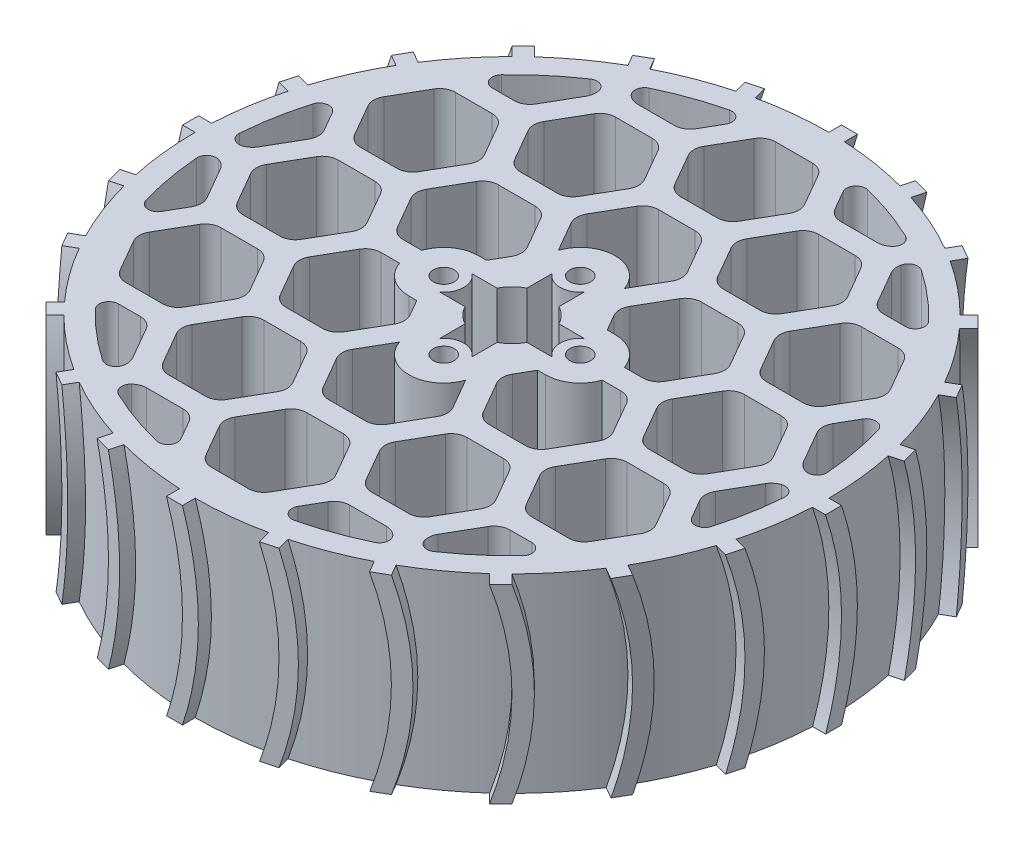
SolidWorks part; units mm, degrees
ref_plane "Front Plane" through (0, 0, 0) normal (0, 0, 1) x (1, 0, 0)
ref_plane "Top Plane" through (0, 0, 0) normal (0, 1, 0) x (1, 0, 0)
ref_plane "Right Plane" through (0, 0, 0) normal (1, 0, 0) x (0, 0, -1)
sketch "Sketch2" plane through (0, 0, 0) normal (0, 1, 0) x (1, 0, 0)
  line L0 (-17.7275, -5.0583) -> (-9.768, -5.0583)
  line L1 (-17.7275, 5.0583) -> (-9.768, 5.0583)
  line L2 (-21.548, 11) -> (-11, 11)
  line L3 (-21.548, -11) -> (-11, -11)
  line L4 (-21.548, 0) -> (0, 0) construction
  line L5 (11, 21.548) -> (11, 11)
  line L6 (-11, 21.548) -> (-11, 11)
  line L7 (5.0583, 17.7275) -> (5.0583, 9.768)
  line L8 (-5.0583, 17.7275) -> (-5.0583, 9.768)
  line L9 (21.548, -11) -> (11, -11)
  line L10 (21.548, 11) -> (11, 11)
  line L11 (17.7275, -5.0583) -> (9.768, -5.0583)
  line L12 (17.7275, 5.0583) -> (9.768, 5.0583)
  line L13 (-11, -21.548) -> (-11, -11)
  line L14 (11, -21.548) -> (11, -11)
  line L15 (-5.0583, -17.7275) -> (-5.0583, -9.768)
  line L16 (5.0583, -17.7275) -> (5.0583, -9.768)
  line L17 (0, 0) -> (-12.9904, 7.5) construction
  line L18 (-15.8771, -2.5) -> (-10.1036, -12.5)
  line L19 (-5.7735, -15) -> (5.7735, -15)
  line L20 (10.1036, -12.5) -> (15.8771, -2.5)
  line L21 (15.8771, 2.5) -> (10.1036, 12.5)
  line L22 (5.7735, 15) -> (-5.7735, 15)
  line L23 (-10.1036, 12.5) -> (-15.8771, 2.5)
  arc A0 (-21.548, 11) -> (-21.548, -11) centre (-21.548, 0) ccw
  arc A1 (-5.0583, 9.768) -> (-9.768, 5.0583) centre (0, 0) ccw
  circle A2 centre (-21.548, 0) radius 3.302
  circle A3 centre (-21.548, 0) radius 6.339
  arc A4 (-5.0583, 9.768) -> (-9.768, 5.0583) centre (0, 0) ccw
  arc A5 (11, 21.548) -> (-11, 21.548) centre (0, 21.548) ccw
  circle A6 centre (0, 21.548) radius 6.339
  circle A7 centre (0, 21.548) radius 3.302
  arc A8 (21.548, -11) -> (21.548, 11) centre (21.548, 0) ccw
  circle A9 centre (21.548, 0) radius 6.339
  circle A10 centre (21.548, 0) radius 3.302
  arc A11 (-11, -21.548) -> (11, -21.548) centre (0, -21.548) ccw
  circle A12 centre (0, -21.548) radius 6.339
  circle A13 centre (0, -21.548) radius 3.302
  arc A14 (9.768, 5.0583) -> (5.0583, 9.768) centre (0, 0) ccw
  arc A15 (5.0583, -9.768) -> (9.768, -5.0583) centre (0, 0) ccw
  arc A16 (-9.768, -5.0583) -> (-5.0583, -9.768) centre (0, 0) ccw
  circle A17 centre (0, 0) radius 100
  circle A18 centre (0, 0) radius 15 construction
  arc A19 (10.1036, 12.5) -> (5.7735, 15) centre (5.7735, 10) ccw
  arc A20 (15.8771, -2.5) -> (15.8771, 2.5) centre (11.547, 0) ccw
  arc A21 (10.1036, -12.5) -> (5.7735, -15) centre (5.7735, -10) cw
  arc A22 (-10.1036, -12.5) -> (-5.7735, -15) centre (-5.7735, -10) ccw
  arc A23 (-15.8771, -2.5) -> (-15.8771, 2.5) centre (-11.547, 0) cw
  arc A24 (-10.1036, 12.5) -> (-5.7735, 15) centre (-5.7735, 10) cw
  point P59 (0, 0)
  dimension "D1" = 6.604
  dimension "D2" = 12.678
  dimension "D3" = 11
  dimension "D8" = 22
  dimension "D10" = 200
  dimension "D12" = 5
  dimension "D4" = 21.548
  dimension "D5" = 7.9595
  dimension "D6" = 10.548
  dimension "D7" = 10.548
  dimension "D11" = 30
  dimension "D13" = 30
  dimension "D9" = 4
sketch "Sketch3" plane through (0, 0, 0) normal (0, 1, 0) x (1, 0, 0)
  line L0 (0, 0) -> (16.547, 0) construction
  line L1 (5.7735, 15) -> (-5.7735, 15)
  line L2 (-10.1036, 12.5) -> (-15.8771, 2.5)
  line L3 (-15.8771, -2.5) -> (-10.1036, -12.5)
  line L4 (-5.7735, -15) -> (5.7735, -15)
  line L5 (10.1036, -12.5) -> (15.8771, -2.5)
  line L6 (15.8771, 2.5) -> (10.1036, 12.5)
  line L7 (37.8164, 33.5) -> (26.2694, 33.5)
  line L8 (21.9393, 31) -> (16.1658, 21)
  line L9 (16.1658, 16) -> (21.9393, 6)
  line L10 (26.2694, 3.5) -> (37.8164, 3.5)
  line L11 (42.1466, 6) -> (47.9201, 16)
  line L12 (47.9201, 21) -> (42.1466, 31)
  line L13 (69.8594, 52) -> (58.3124, 52)
  line L14 (53.9823, 49.5) -> (48.2087, 39.5)
  line L15 (48.2087, 34.5) -> (53.9823, 24.5)
  line L16 (58.3124, 22) -> (69.8594, 22)
  line L17 (74.1895, 24.5) -> (79.963, 34.5)
  line L18 (79.963, 39.5) -> (74.1895, 49.5)
  line L19 (101.9023, 70.5) -> (90.3553, 70.5)
  line L20 (86.0252, 68) -> (80.2517, 58)
  line L21 (80.2517, 53) -> (86.0252, 43)
  line L22 (90.3553, 40.5) -> (101.9023, 40.5)
  line L23 (106.2324, 43) -> (112.006, 53)
  line L24 (112.006, 58) -> (106.2324, 68)
  line L25 (37.8164, 70.5) -> (26.2694, 70.5)
  line L26 (21.9393, 68) -> (16.1658, 58)
  line L27 (16.1658, 53) -> (21.9393, 43)
  line L28 (26.2694, 40.5) -> (37.8164, 40.5)
  line L29 (42.1466, 43) -> (47.9201, 53)
  line L30 (47.9201, 58) -> (42.1466, 68)
  line L31 (69.8594, 89) -> (58.3124, 89)
  line L32 (53.9823, 86.5) -> (48.2087, 76.5)
  line L33 (48.2087, 71.5) -> (53.9823, 61.5)
  line L34 (58.3124, 59) -> (69.8594, 59)
  line L35 (74.1895, 61.5) -> (79.963, 71.5)
  line L36 (79.963, 76.5) -> (74.1895, 86.5)
  line L37 (101.9023, 107.5) -> (90.3553, 107.5) [skipped]
  line L38 (86.0252, 105) -> (80.2517, 95) [skipped]
  line L39 (80.2517, 90) -> (86.0252, 80) [skipped]
  line L40 (90.3553, 77.5) -> (101.9023, 77.5) [skipped]
  line L41 (106.2324, 80) -> (112.006, 90) [skipped]
  line L42 (112.006, 95) -> (106.2324, 105) [skipped]
  line L43 (37.8164, 107.5) -> (26.2694, 107.5)
  line L44 (21.9393, 105) -> (16.1658, 95)
  line L45 (16.1658, 90) -> (21.9393, 80)
  line L46 (26.2694, 77.5) -> (37.8164, 77.5)
  line L47 (42.1466, 80) -> (47.9201, 90)
  line L48 (47.9201, 95) -> (42.1466, 105)
  line L49 (69.8594, 126) -> (58.3124, 126) [skipped]
  line L50 (53.9823, 123.5) -> (48.2087, 113.5) [skipped]
  line L51 (48.2087, 108.5) -> (53.9823, 98.5) [skipped]
  line L52 (58.3124, 96) -> (69.8594, 96) [skipped]
  line L53 (74.1895, 98.5) -> (79.963, 108.5) [skipped]
  line L54 (79.963, 113.5) -> (74.1895, 123.5) [skipped]
  line L55 (101.9023, 144.5) -> (90.3553, 144.5) [skipped]
  line L56 (86.0252, 142) -> (80.2517, 132) [skipped]
  line L57 (80.2517, 127) -> (86.0252, 117) [skipped]
  line L58 (90.3553, 114.5) -> (101.9023, 114.5) [skipped]
  line L59 (106.2324, 117) -> (112.006, 127) [skipped]
  line L60 (112.006, 132) -> (106.2324, 142) [skipped]
  line L61 (37.8164, 144.5) -> (26.2694, 144.5) [skipped]
  line L62 (21.9393, 142) -> (16.1658, 132) [skipped]
  line L63 (16.1658, 127) -> (21.9393, 117) [skipped]
  line L64 (26.2694, 114.5) -> (37.8164, 114.5) [skipped]
  line L65 (42.1466, 117) -> (47.9201, 127) [skipped]
  line L66 (47.9201, 132) -> (42.1466, 142) [skipped]
  line L67 (69.8594, 163) -> (58.3124, 163) [skipped]
  line L68 (53.9823, 160.5) -> (48.2087, 150.5) [skipped]
  line L69 (48.2087, 145.5) -> (53.9823, 135.5) [skipped]
  line L70 (58.3124, 133) -> (69.8594, 133) [skipped]
  line L71 (74.1895, 135.5) -> (79.963, 145.5) [skipped]
  line L72 (79.963, 150.5) -> (74.1895, 160.5) [skipped]
  line L73 (101.9023, 181.5) -> (90.3553, 181.5) [skipped]
  line L74 (86.0252, 179) -> (80.2517, 169) [skipped]
  line L75 (80.2517, 164) -> (86.0252, 154) [skipped]
  line L76 (90.3553, 151.5) -> (101.9023, 151.5) [skipped]
  line L77 (106.2324, 154) -> (112.006, 164) [skipped]
  line L78 (112.006, 169) -> (106.2324, 179) [skipped]
  line L79 (5.7735, 52) -> (-5.7735, 52) [skipped]
  line L80 (-10.1036, 49.5) -> (-15.8771, 39.5) [skipped]
  line L81 (-15.8771, 34.5) -> (-10.1036, 24.5) [skipped]
  line L82 (-5.7735, 22) -> (5.7735, 22) [skipped]
  line L83 (10.1036, 24.5) -> (15.8771, 34.5) [skipped]
  line L84 (15.8771, 39.5) -> (10.1036, 49.5) [skipped]
  line L85 (5.7735, 89) -> (-5.7735, 89) [skipped]
  line L86 (-10.1036, 86.5) -> (-15.8771, 76.5) [skipped]
  line L87 (-15.8771, 71.5) -> (-10.1036, 61.5) [skipped]
  line L88 (-5.7735, 59) -> (5.7735, 59) [skipped]
  line L89 (10.1036, 61.5) -> (15.8771, 71.5) [skipped]
  line L90 (15.8771, 76.5) -> (10.1036, 86.5) [skipped]
  line L91 (5.7735, 126) -> (-5.7735, 126) [skipped]
  line L92 (-10.1036, 123.5) -> (-15.8771, 113.5) [skipped]
  line L93 (-15.8771, 108.5) -> (-10.1036, 98.5) [skipped]
  line L94 (-5.7735, 96) -> (5.7735, 96) [skipped]
  line L95 (10.1036, 98.5) -> (15.8771, 108.5) [skipped]
  line L96 (15.8771, 113.5) -> (10.1036, 123.5) [skipped]
  line L97 (0, 0) -> (83.1384, 48) construction
  line L98 (112.006, 21) -> (106.2324, 31)
  line L99 (101.9023, 33.5) -> (90.3553, 33.5)
  line L100 (86.0252, 31) -> (80.2517, 21)
  line L101 (80.2517, 16) -> (86.0252, 6)
  line L102 (90.3553, 3.5) -> (101.9023, 3.5)
  line L103 (106.2324, 6) -> (112.006, 16)
  line L104 (112.006, -16) -> (106.2324, -6)
  line L105 (101.9023, -3.5) -> (90.3553, -3.5)
  line L106 (86.0252, -6) -> (80.2517, -16)
  line L107 (80.2517, -21) -> (86.0252, -31)
  line L108 (90.3553, -33.5) -> (101.9023, -33.5)
  line L109 (106.2324, -31) -> (112.006, -21)
  line L110 (112.006, -53) -> (106.2324, -43)
  line L111 (101.9023, -40.5) -> (90.3553, -40.5)
  line L112 (86.0252, -43) -> (80.2517, -53)
  line L113 (80.2517, -58) -> (86.0252, -68)
  line L114 (90.3553, -70.5) -> (101.9023, -70.5)
  line L115 (106.2324, -68) -> (112.006, -58)
  line L116 (79.963, -34.5) -> (74.1895, -24.5)
  line L117 (69.8594, -22) -> (58.3124, -22)
  line L118 (53.9823, -24.5) -> (48.2087, -34.5)
  line L119 (48.2087, -39.5) -> (53.9823, -49.5)
  line L120 (58.3124, -52) -> (69.8594, -52)
  line L121 (74.1895, -49.5) -> (79.963, -39.5)
  line L122 (79.963, 2.5) -> (74.1895, 12.5)
  line L123 (69.8594, 15) -> (58.3124, 15)
  line L124 (53.9823, 12.5) -> (48.2087, 2.5)
  line L125 (48.2087, -2.5) -> (53.9823, -12.5)
  line L126 (58.3124, -15) -> (69.8594, -15)
  line L127 (74.1895, -12.5) -> (79.963, -2.5)
  line L128 (47.9201, -16) -> (42.1466, -6)
  line L129 (37.8164, -3.5) -> (26.2694, -3.5)
  line L130 (21.9393, -6) -> (16.1658, -16)
  line L131 (16.1658, -21) -> (21.9393, -31)
  line L132 (26.2694, -33.5) -> (37.8164, -33.5)
  line L133 (42.1466, -31) -> (47.9201, -21)
  line L134 (74.1895, -86.5) -> (79.963, -76.5)
  line L135 (79.963, -71.5) -> (74.1895, -61.5)
  line L136 (69.8594, -59) -> (58.3124, -59)
  line L137 (53.9823, -61.5) -> (48.2087, -71.5)
  line L138 (48.2087, -76.5) -> (53.9823, -86.5)
  line L139 (58.3124, -89) -> (69.8594, -89)
  line L140 (42.1466, -105) -> (47.9201, -95)
  line L141 (47.9201, -90) -> (42.1466, -80)
  line L142 (37.8164, -77.5) -> (26.2694, -77.5)
  line L143 (21.9393, -80) -> (16.1658, -90)
  line L144 (16.1658, -95) -> (21.9393, -105)
  line L145 (26.2694, -107.5) -> (37.8164, -107.5)
  line L146 (10.1036, -123.5) -> (15.8771, -113.5)
  line L147 (15.8771, -108.5) -> (10.1036, -98.5)
  line L148 (5.7735, -96) -> (-5.7735, -96)
  line L149 (-10.1036, -98.5) -> (-15.8771, -108.5)
  line L150 (-15.8771, -113.5) -> (-10.1036, -123.5)
  line L151 (-5.7735, -126) -> (5.7735, -126)
  line L152 (10.1036, -86.5) -> (15.8771, -76.5)
  line L153 (15.8771, -71.5) -> (10.1036, -61.5)
  line L154 (5.7735, -59) -> (-5.7735, -59)
  line L155 (-10.1036, -61.5) -> (-15.8771, -71.5)
  line L156 (-15.8771, -76.5) -> (-10.1036, -86.5)
  line L157 (-5.7735, -89) -> (5.7735, -89)
  line L158 (42.1466, -68) -> (47.9201, -58)
  line L159 (47.9201, -53) -> (42.1466, -43)
  line L160 (37.8164, -40.5) -> (26.2694, -40.5)
  line L161 (21.9393, -43) -> (16.1658, -53)
  line L162 (16.1658, -58) -> (21.9393, -68)
  line L163 (26.2694, -70.5) -> (37.8164, -70.5)
  line L164 (10.1036, -49.5) -> (15.8771, -39.5)
  line L165 (15.8771, -34.5) -> (10.1036, -24.5)
  line L166 (5.7735, -22) -> (-5.7735, -22)
  line L167 (-10.1036, -24.5) -> (-15.8771, -34.5)
  line L168 (-15.8771, -39.5) -> (-10.1036, -49.5)
  line L169 (-5.7735, -52) -> (5.7735, -52)
  line L170 (-37.8164, -107.5) -> (-26.2694, -107.5)
  line L171 (-21.9393, -105) -> (-16.1658, -95)
  line L172 (-16.1658, -90) -> (-21.9393, -80)
  line L173 (-26.2694, -77.5) -> (-37.8164, -77.5)
  line L174 (-42.1466, -80) -> (-47.9201, -90)
  line L175 (-47.9201, -95) -> (-42.1466, -105)
  line L176 (-69.8594, -89) -> (-58.3124, -89)
  line L177 (-53.9823, -86.5) -> (-48.2087, -76.5)
  line L178 (-48.2087, -71.5) -> (-53.9823, -61.5)
  line L179 (-58.3124, -59) -> (-69.8594, -59)
  line L180 (-74.1895, -61.5) -> (-79.963, -71.5)
  line L181 (-79.963, -76.5) -> (-74.1895, -86.5)
  line L182 (-101.9023, -70.5) -> (-90.3553, -70.5)
  line L183 (-86.0252, -68) -> (-80.2517, -58)
  line L184 (-80.2517, -53) -> (-86.0252, -43)
  line L185 (-90.3553, -40.5) -> (-101.9023, -40.5)
  line L186 (-106.2324, -43) -> (-112.006, -53)
  line L187 (-112.006, -58) -> (-106.2324, -68)
  line L188 (-69.8594, -52) -> (-58.3124, -52)
  line L189 (-53.9823, -49.5) -> (-48.2087, -39.5)
  line L190 (-48.2087, -34.5) -> (-53.9823, -24.5)
  line L191 (-58.3124, -22) -> (-69.8594, -22)
  line L192 (-74.1895, -24.5) -> (-79.963, -34.5)
  line L193 (-79.963, -39.5) -> (-74.1895, -49.5)
  line L194 (-37.8164, -70.5) -> (-26.2694, -70.5)
  line L195 (-21.9393, -68) -> (-16.1658, -58)
  line L196 (-16.1658, -53) -> (-21.9393, -43)
  line L197 (-26.2694, -40.5) -> (-37.8164, -40.5)
  line L198 (-42.1466, -43) -> (-47.9201, -53)
  line L199 (-47.9201, -58) -> (-42.1466, -68)
  line L200 (-37.8164, -33.5) -> (-26.2694, -33.5)
  line L201 (-21.9393, -31) -> (-16.1658, -21)
  line L202 (-16.1658, -16) -> (-21.9393, -6)
  line L203 (-26.2694, -3.5) -> (-37.8164, -3.5)
  line L204 (-42.1466, -6) -> (-47.9201, -16)
  line L205 (-47.9201, -21) -> (-42.1466, -31)
  line L206 (-112.006, -21) -> (-106.2324, -31)
  line L207 (-101.9023, -33.5) -> (-90.3553, -33.5)
  line L208 (-86.0252, -31) -> (-80.2517, -21)
  line L209 (-80.2517, -16) -> (-86.0252, -6)
  line L210 (-90.3553, -3.5) -> (-101.9023, -3.5)
  line L211 (-106.2324, -6) -> (-112.006, -16)
  line L212 (-112.006, 16) -> (-106.2324, 6)
  line L213 (-101.9023, 3.5) -> (-90.3553, 3.5)
  line L214 (-86.0252, 6) -> (-80.2517, 16)
  line L215 (-80.2517, 21) -> (-86.0252, 31)
  line L216 (-90.3553, 33.5) -> (-101.9023, 33.5)
  line L217 (-106.2324, 31) -> (-112.006, 21)
  line L218 (-112.006, 53) -> (-106.2324, 43)
  line L219 (-101.9023, 40.5) -> (-90.3553, 40.5)
  line L220 (-86.0252, 43) -> (-80.2517, 53)
  line L221 (-80.2517, 58) -> (-86.0252, 68)
  line L222 (-90.3553, 70.5) -> (-101.9023, 70.5)
  line L223 (-106.2324, 68) -> (-112.006, 58)
  line L224 (-79.963, 34.5) -> (-74.1895, 24.5)
  line L225 (-69.8594, 22) -> (-58.3124, 22)
  line L226 (-53.9823, 24.5) -> (-48.2087, 34.5)
  line L227 (-48.2087, 39.5) -> (-53.9823, 49.5)
  line L228 (-58.3124, 52) -> (-69.8594, 52)
  line L229 (-74.1895, 49.5) -> (-79.963, 39.5)
  line L230 (-79.963, -2.5) -> (-74.1895, -12.5)
  line L231 (-69.8594, -15) -> (-58.3124, -15)
  line L232 (-53.9823, -12.5) -> (-48.2087, -2.5)
  line L233 (-48.2087, 2.5) -> (-53.9823, 12.5)
  line L234 (-58.3124, 15) -> (-69.8594, 15)
  line L235 (-74.1895, 12.5) -> (-79.963, 2.5)
  line L236 (-47.9201, 16) -> (-42.1466, 6)
  line L237 (-37.8164, 3.5) -> (-26.2694, 3.5)
  line L238 (-21.9393, 6) -> (-16.1658, 16)
  line L239 (-16.1658, 21) -> (-21.9393, 31)
  line L240 (-26.2694, 33.5) -> (-37.8164, 33.5)
  line L241 (-42.1466, 31) -> (-47.9201, 21)
  line L242 (-74.1895, 86.5) -> (-79.963, 76.5)
  line L243 (-79.963, 71.5) -> (-74.1895, 61.5)
  line L244 (-69.8594, 59) -> (-58.3124, 59)
  line L245 (-53.9823, 61.5) -> (-48.2087, 71.5)
  line L246 (-48.2087, 76.5) -> (-53.9823, 86.5)
  line L247 (-58.3124, 89) -> (-69.8594, 89)
  line L248 (-42.1466, 105) -> (-47.9201, 95)
  line L249 (-47.9201, 90) -> (-42.1466, 80)
  line L250 (-37.8164, 77.5) -> (-26.2694, 77.5)
  line L251 (-21.9393, 80) -> (-16.1658, 90)
  line L252 (-16.1658, 95) -> (-21.9393, 105)
  line L253 (-26.2694, 107.5) -> (-37.8164, 107.5)
  line L254 (-10.1036, 123.5) -> (-15.8771, 113.5)
  line L255 (-15.8771, 108.5) -> (-10.1036, 98.5)
  line L256 (-5.7735, 96) -> (5.7735, 96)
  line L257 (10.1036, 98.5) -> (15.8771, 108.5)
  line L258 (15.8771, 113.5) -> (10.1036, 123.5)
  line L259 (5.7735, 126) -> (-5.7735, 126)
  line L260 (-10.1036, 86.5) -> (-15.8771, 76.5)
  line L261 (-15.8771, 71.5) -> (-10.1036, 61.5)
  line L262 (-5.7735, 59) -> (5.7735, 59)
  line L263 (10.1036, 61.5) -> (15.8771, 71.5)
  line L264 (15.8771, 76.5) -> (10.1036, 86.5)
  line L265 (5.7735, 89) -> (-5.7735, 89)
  line L266 (-42.1466, 68) -> (-47.9201, 58)
  line L267 (-47.9201, 53) -> (-42.1466, 43)
  line L268 (-37.8164, 40.5) -> (-26.2694, 40.5)
  line L269 (-21.9393, 43) -> (-16.1658, 53)
  line L270 (-16.1658, 58) -> (-21.9393, 68)
  line L271 (-26.2694, 70.5) -> (-37.8164, 70.5)
  line L272 (-10.1036, 49.5) -> (-15.8771, 39.5)
  line L273 (-15.8771, 34.5) -> (-10.1036, 24.5)
  line L274 (-5.7735, 22) -> (5.7735, 22)
  line L275 (10.1036, 24.5) -> (15.8771, 34.5)
  line L276 (15.8771, 39.5) -> (10.1036, 49.5)
  line L277 (5.7735, 52) -> (-5.7735, 52)
  line L278 (0, 0) -> (0, 96) construction
  line L279 (0, 0) -> (-83.1384, 48) construction
  line L280 (-17.7275, -5.0583) -> (-9.768, -5.0583)
  line L281 (-17.7275, 5.0583) -> (-9.768, 5.0583)
  line L282 (-21.548, 11) -> (-11, 11)
  line L283 (-21.548, -11) -> (-11, -11)
  line L284 (0, 0) -> (-21.548, 0) construction
  line L285 (11, 21.548) -> (11, 11)
  line L286 (-11, 21.548) -> (-11, 11)
  line L287 (-5.0583, 17.7275) -> (-5.0583, 9.768)
  line L288 (5.0583, 17.7275) -> (5.0583, 9.768)
  line L289 (21.548, -11) -> (11, -11)
  line L290 (21.548, 11) -> (11, 11)
  line L291 (17.7275, 5.0583) -> (9.768, 5.0583)
  line L292 (17.7275, -5.0583) -> (9.768, -5.0583)
  line L293 (-11, -21.548) -> (-11, -11)
  line L294 (11, -21.548) -> (11, -11)
  line L295 (5.0583, -17.7275) -> (5.0583, -9.768)
  line L296 (-5.0583, -17.7275) -> (-5.0583, -9.768)
  line L297 (0, 0) -> (0, 21.548) construction
  circle A0 centre (0, 0) radius 15 construction
  arc A1 (10.1036, 12.5) -> (5.7735, 15) centre (5.7735, 10) ccw
  arc A2 (15.8771, 2.5) -> (15.8771, -2.5) centre (11.547, 0) cw
  arc A3 (5.7735, -15) -> (10.1036, -12.5) centre (5.7735, -10) ccw
  arc A4 (-5.7735, -15) -> (-10.1036, -12.5) centre (-5.7735, -10) cw
  arc A5 (-15.8771, -2.5) -> (-15.8771, 2.5) centre (-11.547, 0) cw
  arc A6 (-10.1036, 12.5) -> (-5.7735, 15) centre (-5.7735, 10) cw
  circle A7 centre (0, 0) radius 100
  arc A8 (21.9393, 31) -> (26.2694, 33.5) centre (26.2694, 28.5) cw
  arc A9 (42.1466, 31) -> (37.8164, 33.5) centre (37.8164, 28.5) ccw
  arc A10 (16.1658, 16) -> (16.1658, 21) centre (20.4959, 18.5) cw
  arc A11 (26.2694, 3.5) -> (21.9393, 6) centre (26.2694, 8.5) cw
  arc A12 (37.8164, 3.5) -> (42.1466, 6) centre (37.8164, 8.5) ccw
  arc A13 (47.9201, 21) -> (47.9201, 16) centre (43.5899, 18.5) cw
  arc A14 (53.9823, 49.5) -> (58.3124, 52) centre (58.3124, 47) cw
  arc A15 (74.1895, 49.5) -> (69.8594, 52) centre (69.8594, 47) ccw
  arc A16 (48.2087, 34.5) -> (48.2087, 39.5) centre (52.5389, 37) cw
  arc A17 (58.3124, 22) -> (53.9823, 24.5) centre (58.3124, 27) cw
  arc A18 (69.8594, 22) -> (74.1895, 24.5) centre (69.8594, 27) ccw
  arc A19 (79.963, 39.5) -> (79.963, 34.5) centre (75.6329, 37) cw
  arc A20 (86.0252, 68) -> (90.3553, 70.5) centre (90.3553, 65.5) cw
  arc A21 (106.2324, 68) -> (101.9023, 70.5) centre (101.9023, 65.5) ccw
  arc A22 (80.2517, 53) -> (80.2517, 58) centre (84.5818, 55.5) cw
  arc A23 (90.3553, 40.5) -> (86.0252, 43) centre (90.3553, 45.5) cw
  arc A24 (101.9023, 40.5) -> (106.2324, 43) centre (101.9023, 45.5) ccw
  arc A25 (112.006, 58) -> (112.006, 53) centre (107.6758, 55.5) cw
  arc A26 (21.9393, 68) -> (26.2694, 70.5) centre (26.2694, 65.5) cw
  arc A27 (42.1466, 68) -> (37.8164, 70.5) centre (37.8164, 65.5) ccw
  arc A28 (16.1658, 53) -> (16.1658, 58) centre (20.4959, 55.5) cw
  arc A29 (26.2694, 40.5) -> (21.9393, 43) centre (26.2694, 45.5) cw
  arc A30 (37.8164, 40.5) -> (42.1466, 43) centre (37.8164, 45.5) ccw
  arc A31 (47.9201, 58) -> (47.9201, 53) centre (43.5899, 55.5) cw
  arc A32 (53.9823, 86.5) -> (58.3124, 89) centre (58.3124, 84) cw
  arc A33 (74.1895, 86.5) -> (69.8594, 89) centre (69.8594, 84) ccw
  arc A34 (48.2087, 71.5) -> (48.2087, 76.5) centre (52.5389, 74) cw
  arc A35 (58.3124, 59) -> (53.9823, 61.5) centre (58.3124, 64) cw
  arc A36 (69.8594, 59) -> (74.1895, 61.5) centre (69.8594, 64) ccw
  arc A37 (79.963, 76.5) -> (79.963, 71.5) centre (75.6329, 74) cw
  arc A38 (86.0252, 105) -> (90.3553, 107.5) centre (90.3553, 102.5) cw [skipped]
  arc A39 (106.2324, 105) -> (101.9023, 107.5) centre (101.9023, 102.5) ccw [skipped]
  arc A40 (80.2517, 90) -> (80.2517, 95) centre (84.5818, 92.5) cw [skipped]
  arc A41 (90.3553, 77.5) -> (86.0252, 80) centre (90.3553, 82.5) cw [skipped]
  arc A42 (101.9023, 77.5) -> (106.2324, 80) centre (101.9023, 82.5) ccw [skipped]
  arc A43 (112.006, 95) -> (112.006, 90) centre (107.6758, 92.5) cw [skipped]
  arc A44 (21.9393, 105) -> (26.2694, 107.5) centre (26.2694, 102.5) cw
  arc A45 (42.1466, 105) -> (37.8164, 107.5) centre (37.8164, 102.5) ccw
  arc A46 (16.1658, 90) -> (16.1658, 95) centre (20.4959, 92.5) cw
  arc A47 (26.2694, 77.5) -> (21.9393, 80) centre (26.2694, 82.5) cw
  arc A48 (37.8164, 77.5) -> (42.1466, 80) centre (37.8164, 82.5) ccw
  arc A49 (47.9201, 95) -> (47.9201, 90) centre (43.5899, 92.5) cw
  arc A50 (53.9823, 123.5) -> (58.3124, 126) centre (58.3124, 121) cw [skipped]
  arc A51 (74.1895, 123.5) -> (69.8594, 126) centre (69.8594, 121) ccw [skipped]
  arc A52 (48.2087, 108.5) -> (48.2087, 113.5) centre (52.5389, 111) cw [skipped]
  arc A53 (58.3124, 96) -> (53.9823, 98.5) centre (58.3124, 101) cw [skipped]
  arc A54 (69.8594, 96) -> (74.1895, 98.5) centre (69.8594, 101) ccw [skipped]
  arc A55 (79.963, 113.5) -> (79.963, 108.5) centre (75.6329, 111) cw [skipped]
  arc A56 (86.0252, 142) -> (90.3553, 144.5) centre (90.3553, 139.5) cw [skipped]
  arc A57 (106.2324, 142) -> (101.9023, 144.5) centre (101.9023, 139.5) ccw [skipped]
  arc A58 (80.2517, 127) -> (80.2517, 132) centre (84.5818, 129.5) cw [skipped]
  arc A59 (90.3553, 114.5) -> (86.0252, 117) centre (90.3553, 119.5) cw [skipped]
  arc A60 (101.9023, 114.5) -> (106.2324, 117) centre (101.9023, 119.5) ccw [skipped]
  arc A61 (112.006, 132) -> (112.006, 127) centre (107.6758, 129.5) cw [skipped]
  arc A62 (21.9393, 142) -> (26.2694, 144.5) centre (26.2694, 139.5) cw [skipped]
  arc A63 (42.1466, 142) -> (37.8164, 144.5) centre (37.8164, 139.5) ccw [skipped]
  arc A64 (16.1658, 127) -> (16.1658, 132) centre (20.4959, 129.5) cw [skipped]
  arc A65 (26.2694, 114.5) -> (21.9393, 117) centre (26.2694, 119.5) cw [skipped]
  arc A66 (37.8164, 114.5) -> (42.1466, 117) centre (37.8164, 119.5) ccw [skipped]
  arc A67 (47.9201, 132) -> (47.9201, 127) centre (43.5899, 129.5) cw [skipped]
  arc A68 (53.9823, 160.5) -> (58.3124, 163) centre (58.3124, 158) cw [skipped]
  arc A69 (74.1895, 160.5) -> (69.8594, 163) centre (69.8594, 158) ccw [skipped]
  arc A70 (48.2087, 145.5) -> (48.2087, 150.5) centre (52.5389, 148) cw [skipped]
  arc A71 (58.3124, 133) -> (53.9823, 135.5) centre (58.3124, 138) cw [skipped]
  arc A72 (69.8594, 133) -> (74.1895, 135.5) centre (69.8594, 138) ccw [skipped]
  arc A73 (79.963, 150.5) -> (79.963, 145.5) centre (75.6329, 148) cw [skipped]
  arc A74 (86.0252, 179) -> (90.3553, 181.5) centre (90.3553, 176.5) cw [skipped]
  arc A75 (106.2324, 179) -> (101.9023, 181.5) centre (101.9023, 176.5) ccw [skipped]
  arc A76 (80.2517, 164) -> (80.2517, 169) centre (84.5818, 166.5) cw [skipped]
  arc A77 (90.3553, 151.5) -> (86.0252, 154) centre (90.3553, 156.5) cw [skipped]
  arc A78 (101.9023, 151.5) -> (106.2324, 154) centre (101.9023, 156.5) ccw [skipped]
  arc A79 (112.006, 169) -> (112.006, 164) centre (107.6758, 166.5) cw [skipped]
  arc A80 (-10.1036, 49.5) -> (-5.7735, 52) centre (-5.7735, 47) cw [skipped]
  arc A81 (10.1036, 49.5) -> (5.7735, 52) centre (5.7735, 47) ccw [skipped]
  arc A82 (-15.8771, 34.5) -> (-15.8771, 39.5) centre (-11.547, 37) cw [skipped]
  arc A83 (-5.7735, 22) -> (-10.1036, 24.5) centre (-5.7735, 27) cw [skipped]
  arc A84 (5.7735, 22) -> (10.1036, 24.5) centre (5.7735, 27) ccw [skipped]
  arc A85 (15.8771, 39.5) -> (15.8771, 34.5) centre (11.547, 37) cw [skipped]
  arc A86 (-10.1036, 86.5) -> (-5.7735, 89) centre (-5.7735, 84) cw [skipped]
  arc A87 (10.1036, 86.5) -> (5.7735, 89) centre (5.7735, 84) ccw [skipped]
  arc A88 (-15.8771, 71.5) -> (-15.8771, 76.5) centre (-11.547, 74) cw [skipped]
  arc A89 (-5.7735, 59) -> (-10.1036, 61.5) centre (-5.7735, 64) cw [skipped]
  arc A90 (5.7735, 59) -> (10.1036, 61.5) centre (5.7735, 64) ccw [skipped]
  arc A91 (15.8771, 76.5) -> (15.8771, 71.5) centre (11.547, 74) cw [skipped]
  arc A92 (-10.1036, 123.5) -> (-5.7735, 126) centre (-5.7735, 121) cw [skipped]
  arc A93 (10.1036, 123.5) -> (5.7735, 126) centre (5.7735, 121) ccw [skipped]
  arc A94 (-15.8771, 108.5) -> (-15.8771, 113.5) centre (-11.547, 111) cw [skipped]
  arc A95 (-5.7735, 96) -> (-10.1036, 98.5) centre (-5.7735, 101) cw [skipped]
  arc A96 (5.7735, 96) -> (10.1036, 98.5) centre (5.7735, 101) ccw [skipped]
  arc A97 (15.8771, 113.5) -> (15.8771, 108.5) centre (11.547, 111) cw [skipped]
  arc A98 (101.9023, 33.5) -> (106.2324, 31) centre (101.9023, 28.5) cw
  arc A99 (86.0252, 31) -> (90.3553, 33.5) centre (90.3553, 28.5) cw
  arc A100 (80.2517, 16) -> (80.2517, 21) centre (84.5818, 18.5) cw
  arc A101 (86.0252, 6) -> (90.3553, 3.5) centre (90.3553, 8.5) ccw
  arc A102 (106.2324, 6) -> (101.9023, 3.5) centre (101.9023, 8.5) cw
  arc A103 (112.006, 16) -> (112.006, 21) centre (107.6758, 18.5) ccw
  arc A104 (101.9023, -3.5) -> (106.2324, -6) centre (101.9023, -8.5) cw
  arc A105 (86.0252, -6) -> (90.3553, -3.5) centre (90.3553, -8.5) cw
  arc A106 (80.2517, -21) -> (80.2517, -16) centre (84.5818, -18.5) cw
  arc A107 (86.0252, -31) -> (90.3553, -33.5) centre (90.3553, -28.5) ccw
  arc A108 (106.2324, -31) -> (101.9023, -33.5) centre (101.9023, -28.5) cw
  arc A109 (112.006, -21) -> (112.006, -16) centre (107.6758, -18.5) ccw
  arc A110 (101.9023, -40.5) -> (106.2324, -43) centre (101.9023, -45.5) cw
  arc A111 (86.0252, -43) -> (90.3553, -40.5) centre (90.3553, -45.5) cw
  arc A112 (80.2517, -58) -> (80.2517, -53) centre (84.5818, -55.5) cw
  arc A113 (86.0252, -68) -> (90.3553, -70.5) centre (90.3553, -65.5) ccw
  arc A114 (106.2324, -68) -> (101.9023, -70.5) centre (101.9023, -65.5) cw
  arc A115 (112.006, -58) -> (112.006, -53) centre (107.6758, -55.5) ccw
  arc A116 (69.8594, -22) -> (74.1895, -24.5) centre (69.8594, -27) cw
  arc A117 (53.9823, -24.5) -> (58.3124, -22) centre (58.3124, -27) cw
  arc A118 (48.2087, -39.5) -> (48.2087, -34.5) centre (52.5389, -37) cw
  arc A119 (53.9823, -49.5) -> (58.3124, -52) centre (58.3124, -47) ccw
  arc A120 (74.1895, -49.5) -> (69.8594, -52) centre (69.8594, -47) cw
  arc A121 (79.963, -39.5) -> (79.963, -34.5) centre (75.6329, -37) ccw
  arc A122 (69.8594, 15) -> (74.1895, 12.5) centre (69.8594, 10) cw
  arc A123 (53.9823, 12.5) -> (58.3124, 15) centre (58.3124, 10) cw
  arc A124 (48.2087, -2.5) -> (48.2087, 2.5) centre (52.5389, 0) cw
  arc A125 (53.9823, -12.5) -> (58.3124, -15) centre (58.3124, -10) ccw
  arc A126 (74.1895, -12.5) -> (69.8594, -15) centre (69.8594, -10) cw
  arc A127 (79.963, -2.5) -> (79.963, 2.5) centre (75.6329, 0) ccw
  arc A128 (37.8164, -3.5) -> (42.1466, -6) centre (37.8164, -8.5) cw
  arc A129 (21.9393, -6) -> (26.2694, -3.5) centre (26.2694, -8.5) cw
  arc A130 (16.1658, -21) -> (16.1658, -16) centre (20.4959, -18.5) cw
  arc A131 (21.9393, -31) -> (26.2694, -33.5) centre (26.2694, -28.5) ccw
  arc A132 (42.1466, -31) -> (37.8164, -33.5) centre (37.8164, -28.5) cw
  arc A133 (47.9201, -21) -> (47.9201, -16) centre (43.5899, -18.5) ccw
  arc A134 (79.963, -71.5) -> (79.963, -76.5) centre (75.6329, -74) cw
  arc A135 (69.8594, -59) -> (74.1895, -61.5) centre (69.8594, -64) cw
  arc A136 (53.9823, -61.5) -> (58.3124, -59) centre (58.3124, -64) cw
  arc A137 (48.2087, -71.5) -> (48.2087, -76.5) centre (52.5389, -74) ccw
  arc A138 (58.3124, -89) -> (53.9823, -86.5) centre (58.3124, -84) cw
  arc A139 (69.8594, -89) -> (74.1895, -86.5) centre (69.8594, -84) ccw
  arc A140 (47.9201, -90) -> (47.9201, -95) centre (43.5899, -92.5) cw
  arc A141 (37.8164, -77.5) -> (42.1466, -80) centre (37.8164, -82.5) cw
  arc A142 (21.9393, -80) -> (26.2694, -77.5) centre (26.2694, -82.5) cw
  arc A143 (16.1658, -90) -> (16.1658, -95) centre (20.4959, -92.5) ccw
  arc A144 (26.2694, -107.5) -> (21.9393, -105) centre (26.2694, -102.5) cw
  arc A145 (37.8164, -107.5) -> (42.1466, -105) centre (37.8164, -102.5) ccw
  arc A146 (15.8771, -108.5) -> (15.8771, -113.5) centre (11.547, -111) cw
  arc A147 (5.7735, -96) -> (10.1036, -98.5) centre (5.7735, -101) cw
  arc A148 (-10.1036, -98.5) -> (-5.7735, -96) centre (-5.7735, -101) cw
  arc A149 (-15.8771, -108.5) -> (-15.8771, -113.5) centre (-11.547, -111) ccw
  arc A150 (-5.7735, -126) -> (-10.1036, -123.5) centre (-5.7735, -121) cw
  arc A151 (5.7735, -126) -> (10.1036, -123.5) centre (5.7735, -121) ccw
  arc A152 (15.8771, -71.5) -> (15.8771, -76.5) centre (11.547, -74) cw
  arc A153 (5.7735, -59) -> (10.1036, -61.5) centre (5.7735, -64) cw
  arc A154 (-10.1036, -61.5) -> (-5.7735, -59) centre (-5.7735, -64) cw
  arc A155 (-15.8771, -71.5) -> (-15.8771, -76.5) centre (-11.547, -74) ccw
  arc A156 (-5.7735, -89) -> (-10.1036, -86.5) centre (-5.7735, -84) cw
  arc A157 (5.7735, -89) -> (10.1036, -86.5) centre (5.7735, -84) ccw
  arc A158 (47.9201, -53) -> (47.9201, -58) centre (43.5899, -55.5) cw
  arc A159 (37.8164, -40.5) -> (42.1466, -43) centre (37.8164, -45.5) cw
  arc A160 (21.9393, -43) -> (26.2694, -40.5) centre (26.2694, -45.5) cw
  arc A161 (16.1658, -53) -> (16.1658, -58) centre (20.4959, -55.5) ccw
  arc A162 (26.2694, -70.5) -> (21.9393, -68) centre (26.2694, -65.5) cw
  arc A163 (37.8164, -70.5) -> (42.1466, -68) centre (37.8164, -65.5) ccw
  arc A164 (15.8771, -34.5) -> (15.8771, -39.5) centre (11.547, -37) cw
  arc A165 (5.7735, -22) -> (10.1036, -24.5) centre (5.7735, -27) cw
  arc A166 (-10.1036, -24.5) -> (-5.7735, -22) centre (-5.7735, -27) cw
  arc A167 (-15.8771, -34.5) -> (-15.8771, -39.5) centre (-11.547, -37) ccw
  arc A168 (-5.7735, -52) -> (-10.1036, -49.5) centre (-5.7735, -47) cw
  arc A169 (5.7735, -52) -> (10.1036, -49.5) centre (5.7735, -47) ccw
  arc A170 (-21.9393, -105) -> (-26.2694, -107.5) centre (-26.2694, -102.5) cw
  arc A171 (-16.1658, -90) -> (-16.1658, -95) centre (-20.4959, -92.5) cw
  arc A172 (-26.2694, -77.5) -> (-21.9393, -80) centre (-26.2694, -82.5) cw
  arc A173 (-37.8164, -77.5) -> (-42.1466, -80) centre (-37.8164, -82.5) ccw
  arc A174 (-47.9201, -95) -> (-47.9201, -90) centre (-43.5899, -92.5) cw
  arc A175 (-42.1466, -105) -> (-37.8164, -107.5) centre (-37.8164, -102.5) ccw
  arc A176 (-53.9823, -86.5) -> (-58.3124, -89) centre (-58.3124, -84) cw
  arc A177 (-48.2087, -71.5) -> (-48.2087, -76.5) centre (-52.5389, -74) cw
  arc A178 (-58.3124, -59) -> (-53.9823, -61.5) centre (-58.3124, -64) cw
  arc A179 (-69.8594, -59) -> (-74.1895, -61.5) centre (-69.8594, -64) ccw
  arc A180 (-79.963, -76.5) -> (-79.963, -71.5) centre (-75.6329, -74) cw
  arc A181 (-74.1895, -86.5) -> (-69.8594, -89) centre (-69.8594, -84) ccw
  arc A182 (-86.0252, -68) -> (-90.3553, -70.5) centre (-90.3553, -65.5) cw
  arc A183 (-80.2517, -53) -> (-80.2517, -58) centre (-84.5818, -55.5) cw
  arc A184 (-90.3553, -40.5) -> (-86.0252, -43) centre (-90.3553, -45.5) cw
  arc A185 (-101.9023, -40.5) -> (-106.2324, -43) centre (-101.9023, -45.5) ccw
  arc A186 (-112.006, -58) -> (-112.006, -53) centre (-107.6758, -55.5) cw
  arc A187 (-106.2324, -68) -> (-101.9023, -70.5) centre (-101.9023, -65.5) ccw
  arc A188 (-53.9823, -49.5) -> (-58.3124, -52) centre (-58.3124, -47) cw
  arc A189 (-48.2087, -34.5) -> (-48.2087, -39.5) centre (-52.5389, -37) cw
  arc A190 (-58.3124, -22) -> (-53.9823, -24.5) centre (-58.3124, -27) cw
  arc A191 (-69.8594, -22) -> (-74.1895, -24.5) centre (-69.8594, -27) ccw
  arc A192 (-79.963, -39.5) -> (-79.963, -34.5) centre (-75.6329, -37) cw
  arc A193 (-74.1895, -49.5) -> (-69.8594, -52) centre (-69.8594, -47) ccw
  arc A194 (-21.9393, -68) -> (-26.2694, -70.5) centre (-26.2694, -65.5) cw
  arc A195 (-16.1658, -53) -> (-16.1658, -58) centre (-20.4959, -55.5) cw
  arc A196 (-26.2694, -40.5) -> (-21.9393, -43) centre (-26.2694, -45.5) cw
  arc A197 (-37.8164, -40.5) -> (-42.1466, -43) centre (-37.8164, -45.5) ccw
  arc A198 (-47.9201, -58) -> (-47.9201, -53) centre (-43.5899, -55.5) cw
  arc A199 (-42.1466, -68) -> (-37.8164, -70.5) centre (-37.8164, -65.5) ccw
  arc A200 (-21.9393, -31) -> (-26.2694, -33.5) centre (-26.2694, -28.5) cw
  arc A201 (-16.1658, -16) -> (-16.1658, -21) centre (-20.4959, -18.5) cw
  arc A202 (-26.2694, -3.5) -> (-21.9393, -6) centre (-26.2694, -8.5) cw
  arc A203 (-37.8164, -3.5) -> (-42.1466, -6) centre (-37.8164, -8.5) ccw
  arc A204 (-47.9201, -21) -> (-47.9201, -16) centre (-43.5899, -18.5) cw
  arc A205 (-42.1466, -31) -> (-37.8164, -33.5) centre (-37.8164, -28.5) ccw
  arc A206 (-101.9023, -33.5) -> (-106.2324, -31) centre (-101.9023, -28.5) cw
  arc A207 (-86.0252, -31) -> (-90.3553, -33.5) centre (-90.3553, -28.5) cw
  arc A208 (-80.2517, -16) -> (-80.2517, -21) centre (-84.5818, -18.5) cw
  arc A209 (-86.0252, -6) -> (-90.3553, -3.5) centre (-90.3553, -8.5) ccw
  arc A210 (-106.2324, -6) -> (-101.9023, -3.5) centre (-101.9023, -8.5) cw
  arc A211 (-112.006, -16) -> (-112.006, -21) centre (-107.6758, -18.5) ccw
  arc A212 (-101.9023, 3.5) -> (-106.2324, 6) centre (-101.9023, 8.5) cw
  arc A213 (-86.0252, 6) -> (-90.3553, 3.5) centre (-90.3553, 8.5) cw
  arc A214 (-80.2517, 21) -> (-80.2517, 16) centre (-84.5818, 18.5) cw
  arc A215 (-86.0252, 31) -> (-90.3553, 33.5) centre (-90.3553, 28.5) ccw
  arc A216 (-106.2324, 31) -> (-101.9023, 33.5) centre (-101.9023, 28.5) cw
  arc A217 (-112.006, 21) -> (-112.006, 16) centre (-107.6758, 18.5) ccw
  arc A218 (-101.9023, 40.5) -> (-106.2324, 43) centre (-101.9023, 45.5) cw
  arc A219 (-86.0252, 43) -> (-90.3553, 40.5) centre (-90.3553, 45.5) cw
  arc A220 (-80.2517, 58) -> (-80.2517, 53) centre (-84.5818, 55.5) cw
  arc A221 (-86.0252, 68) -> (-90.3553, 70.5) centre (-90.3553, 65.5) ccw
  arc A222 (-106.2324, 68) -> (-101.9023, 70.5) centre (-101.9023, 65.5) cw
  arc A223 (-112.006, 58) -> (-112.006, 53) centre (-107.6758, 55.5) ccw
  arc A224 (-69.8594, 22) -> (-74.1895, 24.5) centre (-69.8594, 27) cw
  arc A225 (-53.9823, 24.5) -> (-58.3124, 22) centre (-58.3124, 27) cw
  arc A226 (-48.2087, 39.5) -> (-48.2087, 34.5) centre (-52.5389, 37) cw
  arc A227 (-53.9823, 49.5) -> (-58.3124, 52) centre (-58.3124, 47) ccw
  arc A228 (-74.1895, 49.5) -> (-69.8594, 52) centre (-69.8594, 47) cw
  arc A229 (-79.963, 39.5) -> (-79.963, 34.5) centre (-75.6329, 37) ccw
  arc A230 (-69.8594, -15) -> (-74.1895, -12.5) centre (-69.8594, -10) cw
  arc A231 (-53.9823, -12.5) -> (-58.3124, -15) centre (-58.3124, -10) cw
  arc A232 (-48.2087, 2.5) -> (-48.2087, -2.5) centre (-52.5389, 0) cw
  arc A233 (-53.9823, 12.5) -> (-58.3124, 15) centre (-58.3124, 10) ccw
  arc A234 (-74.1895, 12.5) -> (-69.8594, 15) centre (-69.8594, 10) cw
  arc A235 (-79.963, 2.5) -> (-79.963, -2.5) centre (-75.6329, 0) ccw
  arc A236 (-37.8164, 3.5) -> (-42.1466, 6) centre (-37.8164, 8.5) cw
  arc A237 (-21.9393, 6) -> (-26.2694, 3.5) centre (-26.2694, 8.5) cw
  arc A238 (-16.1658, 21) -> (-16.1658, 16) centre (-20.4959, 18.5) cw
  arc A239 (-21.9393, 31) -> (-26.2694, 33.5) centre (-26.2694, 28.5) ccw
  arc A240 (-42.1466, 31) -> (-37.8164, 33.5) centre (-37.8164, 28.5) cw
  arc A241 (-47.9201, 21) -> (-47.9201, 16) centre (-43.5899, 18.5) ccw
  arc A242 (-79.963, 71.5) -> (-79.963, 76.5) centre (-75.6329, 74) cw
  arc A243 (-69.8594, 59) -> (-74.1895, 61.5) centre (-69.8594, 64) cw
  arc A244 (-53.9823, 61.5) -> (-58.3124, 59) centre (-58.3124, 64) cw
  arc A245 (-48.2087, 71.5) -> (-48.2087, 76.5) centre (-52.5389, 74) ccw
  arc A246 (-58.3124, 89) -> (-53.9823, 86.5) centre (-58.3124, 84) cw
  arc A247 (-69.8594, 89) -> (-74.1895, 86.5) centre (-69.8594, 84) ccw
  arc A248 (-47.9201, 90) -> (-47.9201, 95) centre (-43.5899, 92.5) cw
  arc A249 (-37.8164, 77.5) -> (-42.1466, 80) centre (-37.8164, 82.5) cw
  arc A250 (-21.9393, 80) -> (-26.2694, 77.5) centre (-26.2694, 82.5) cw
  arc A251 (-16.1658, 90) -> (-16.1658, 95) centre (-20.4959, 92.5) ccw
  arc A252 (-26.2694, 107.5) -> (-21.9393, 105) centre (-26.2694, 102.5) cw
  arc A253 (-37.8164, 107.5) -> (-42.1466, 105) centre (-37.8164, 102.5) ccw
  arc A254 (-15.8771, 108.5) -> (-15.8771, 113.5) centre (-11.547, 111) cw
  arc A255 (-5.7735, 96) -> (-10.1036, 98.5) centre (-5.7735, 101) cw
  arc A256 (10.1036, 98.5) -> (5.7735, 96) centre (5.7735, 101) cw
  arc A257 (15.8771, 108.5) -> (15.8771, 113.5) centre (11.547, 111) ccw
  arc A258 (5.7735, 126) -> (10.1036, 123.5) centre (5.7735, 121) cw
  arc A259 (-5.7735, 126) -> (-10.1036, 123.5) centre (-5.7735, 121) ccw
  arc A260 (-15.8771, 71.5) -> (-15.8771, 76.5) centre (-11.547, 74) cw
  arc A261 (-5.7735, 59) -> (-10.1036, 61.5) centre (-5.7735, 64) cw
  arc A262 (10.1036, 61.5) -> (5.7735, 59) centre (5.7735, 64) cw
  arc A263 (15.8771, 71.5) -> (15.8771, 76.5) centre (11.547, 74) ccw
  arc A264 (5.7735, 89) -> (10.1036, 86.5) centre (5.7735, 84) cw
  arc A265 (-5.7735, 89) -> (-10.1036, 86.5) centre (-5.7735, 84) ccw
  arc A266 (-47.9201, 53) -> (-47.9201, 58) centre (-43.5899, 55.5) cw
  arc A267 (-37.8164, 40.5) -> (-42.1466, 43) centre (-37.8164, 45.5) cw
  arc A268 (-21.9393, 43) -> (-26.2694, 40.5) centre (-26.2694, 45.5) cw
  arc A269 (-16.1658, 53) -> (-16.1658, 58) centre (-20.4959, 55.5) ccw
  arc A270 (-26.2694, 70.5) -> (-21.9393, 68) centre (-26.2694, 65.5) cw
  arc A271 (-37.8164, 70.5) -> (-42.1466, 68) centre (-37.8164, 65.5) ccw
  arc A272 (-15.8771, 34.5) -> (-15.8771, 39.5) centre (-11.547, 37) cw
  arc A273 (-5.7735, 22) -> (-10.1036, 24.5) centre (-5.7735, 27) cw
  arc A274 (10.1036, 24.5) -> (5.7735, 22) centre (5.7735, 27) cw
  arc A275 (15.8771, 34.5) -> (15.8771, 39.5) centre (11.547, 37) ccw
  arc A276 (5.7735, 52) -> (10.1036, 49.5) centre (5.7735, 47) cw
  arc A277 (-5.7735, 52) -> (-10.1036, 49.5) centre (-5.7735, 47) ccw
  circle A278 centre (0, 0) radius 93
  arc A279 (-21.548, 11) -> (-21.548, -11) centre (-21.548, 0) ccw
  circle A280 centre (-21.548, 0) radius 3.302
  circle A281 centre (-21.548, 0) radius 6.339
  arc A282 (9.768, 5.0583) -> (9.768, -5.0583) centre (0, 0) ccw construction
  circle A283 centre (0, 0) radius 11
  arc A284 (11, 21.548) -> (-11, 21.548) centre (0, 21.548) ccw
  circle A285 centre (0, 21.548) radius 6.339
  circle A286 centre (0, 21.548) radius 3.302
  arc A287 (21.548, -11) -> (21.548, 11) centre (21.548, 0) ccw
  circle A288 centre (21.548, 0) radius 6.339
  circle A289 centre (21.548, 0) radius 3.302
  arc A290 (-11, -21.548) -> (11, -21.548) centre (0, -21.548) ccw
  circle A291 centre (0, -21.548) radius 6.339
  circle A292 centre (0, -21.548) radius 3.302
  point P837 (0, 0)
  point P897 (0, 0)
  dimension "D3" = 5
  dimension "D4" = 200
  dimension "D11" = 7
  dimension "D13" = 6.604
  dimension "D14" = 12.678
  dimension "D15" = 11
  dimension "D16" = 22
  dimension "D1" = 30
  dimension "D2" = 0
  dimension "D7" = 7
  dimension "D8" = 7
  dimension "D9" = 7
  dimension "D12" = 21.548
  dimension "D17" = 7.9595
  dimension "D18" = 10.548
  dimension "D19" = 5.0583
  dimension "D20" = 5.0583
  dimension "D21" = 11
  dimension "D22" = 11
  dimension "D23" = 10.548
  dimension "D24" = 7.9595
  dimension "D5" = 4
  dimension "D6" = 4
  dimension "D10" = 6
  dimension "D25" = 4
extrude "Boss-Extrude1" add sketch "Sketch3" along normal blind 60 contours L141 A278 L138 A137 L137 A136 L136 A135 A107 L107 A106 L106 A105 L105 L102 A101 L101 A100 L100 A99 A36 L34 A35 L33 A34 L32 L47 A48 L46 A47 L45 A46 A251 L251 A250 L250 A249 L249 L246 A245 L245 A244 L244 A243 | A278 L210 A7 L207 A207 | A278 L213 A7 L210 | A278 A215 L216 A7 L213 | A278 A243 L243 A7 L221 A220 L220 A219 L219 L216 A215 | A220 L221 A7 L219 A219 L220 | A278 L246 A7 L243 A243 | A278 L249 A7 L246 | A278 A251 L252 A7 L249 | A278 A46 L44 A7 L257 A256 L256 A255 L255 L252 A251 | A278 L47 A7 L44 A46 | A278 L32 A7 L47 | A278 A36 L35 A7 L32 | A278 A99 L99 A7 L22 A23 L21 A22 L20 L35 A36 | A23 L22 A7 L20 A22 L21 | A256 L257 A7 L255 A255 L256 | A278 L102 A7 L99 A99 | A278 L105 A7 L102 | A278 A107 L108 A7 L105 | A278 A135 L135 A7 L113 A112 L112 A111 L111 L108 A107 | A112 L113 A7 L111 A111 L112 | A278 L138 A7 L135 A135 | A278 L141 A7 L138 | A278 A143 L144 A7 L141 | A278 A171 L171 A7 L149 A148 L148 A147 L147 L144 A143 | A148 L149 A7 L147 A147 L148 | A278 A207 L207 A7 L185 A184 L184 A183 L183 L180 A179 | A184 L185 A7 L183 A183 L184 | A278 A179 L180 A7 L177 | A278 L177 A7 L174 | A278 L174 A7 L171 A171 | A281 L203 A279 L283 L202 | A281 L237 A279 L203 | A281 L238 L282 A279 L237 | A285 A273 L273 A284 L286 L282 L238 A281 L281 L2 A6 L1 L287 | A291 L296 L4 A4 L3 L280 A281 L202 L283 L293 A290 L167 A166 | A285 A274 L275 A284 L273 A273 | A288 L9 L290 L285 A284 L275 A274 A285 L288 L1 A1 L6 L291 | A288 L10 A287 L290 L9 | A288 L129 A287 L10 | A288 L130 L289 A287 L129 | A291 A165 L165 A290 L294 L289 L130 A288 L292 L5 A3 L4 L295 | A291 A166 L167 A290 L165 A165 | A283 L287 L1 A6 L2 L281 | A283 L280 L3 A4 L4 L296 | A283 L295 L4 A3 L5 L292 | A283 L291 L6 A1 L1 L288 region at (8.9743, 0, -9.8307) region at (5.4159, 0, -15.2605) region at (-8.9743, 0, -9.8307) region at (-5.4159, 0, -15.2605) region at (-8.3794, 0, -23.0089) region at (25.6416, 0, -7.3115) region at (-8.9743, 0, 9.8307) region at (8.9743, 0, 9.8307) region at (16.0638, 0, 5.3188) region at (29.9469, 0, 0) region at (-12.4774, 0, 8.9094) region at (25.6416, 0, 7.3115) region at (-25.6416, 0, -7.3115) region at (-29.9469, 0, 0) region at (-25.6416, 0, 7.3115) region at (0, 0, 28.1205) region at (84.8998, 0, -49.0169) region at (82.5097, 0, -47.637) region at (63.2287, 0, -72.3865) region at (94.3029, 0, -18.5644) region at (48.2394, 0, -83.5531) region at (96.4788, 0, 0) region at (78.2623, 0, -45.1848) region at (31.0742, 0, -90.951) region at (0, 0, -95.274) region at (94.3029, 0, 18.5644) region at (0, 0, -98.0338) region at (82.5097, 0, 47.637) region at (-31.0742, 0, -90.951) region at (84.8998, 0, 49.0169) region at (-48.2394, 0, -83.5531) region at (63.2287, 0, 72.3865) region at (-63.2287, 0, -72.3865) region at (48.2394, 0, 83.5531) region at (-82.5097, 0, -47.637) region at (31.0742, 0, 90.951) region at (-94.3029, 0, -18.5644) region at (0, 0, 95.274) region at (-84.8998, 0, -49.0169) region at (-96.4788, 0, 0) region at (-31.0742, 0, 90.951) region at (-94.3029, 0, 18.5644) region at (0, 0, 98.0338) region at (-48.2394, 0, 83.5531) region at (-82.5097, 0, 47.637) region at (-63.2287, 0, 72.3865) region at (-84.8998, 0, 49.0169)
extrude "Boss-Extrude2" add sketch "Sketch3<3>" along normal blind 60 contours A286 L274 A274 A285 A273 | A286 L274 A273 A285 A274 | L129 A288 L10 A11 L9 L6 A2 L5 L130 A129 A289 | L10 A288 L9 A11 | L130 A288 L129 A129 | L6 A288 L5 A2 | A292 L166 A165 A291 A166 | A292 L166 A166 A291 A165 | L2 A281 L238 A237 L237 L203 A202 L202 L3 A5 A280 | L3 A281 L2 A5 | L238 A281 L237 A237 | L203 A281 L202 A202 region at (0, 0, -15.353) region at (16.7463, 0, -3.8646) region at (15.8617, 0, 0) region at (0, 0, -24.9063) region at (24.2449, 0, -4.8518) region at (-15.8617, 0, 0) region at (-15.9853, 0, -2.6631) region at (24.2449, 0, 4.8518) region at (-24.2449, 0, -4.8518) region at (-24.2449, 0, 4.8518) region at (0, 0, 15.353) region at (0, 0, 24.9063)
sketch "Sketch3<3>" plane through (0, 0, 0) normal (0, 1, 0) x (1, 0, 0) same geometry as "Sketch3"
fillet "Fillet2" radius 3 24 edges at (92.9341, 30, -3.5) (87.1858, 30, -32.3671) (92.9341, 30, 3.5) (87.1858, 30, 32.3671) (71.6236, 30, 59.3216) (49.4981, 30, 78.7333) (43.436, 30, 82.2333) (15.5622, 30, 91.6887) (-15.5622, 30, 91.6887) (-43.436, 30, 82.2333) (-49.4981, 30, 78.7333) (-71.6236, 30, 59.3216) (-87.1858, 30, 32.3671) (-92.9341, 30, 3.5) (-92.9341, 30, -3.5) (-87.1858, 30, -32.3671) (-43.436, 30, -82.2333) (-49.4981, 30, -78.7333) (-71.6236, 30, -59.3216) (-15.5622, 30, -91.6887) (15.5622, 30, -91.6887) (43.436, 30, -82.2333) (49.4981, 30, -78.7333) (71.6236, 30, -59.3216)
ref_plane "Plane1" through (100, 0, 0) normal (1, 0, 0) x (0, 0, -1)
sketch "Sketch4" plane through (100, 0, 0) normal (1, 0, 0) x (0, 0, -1)
  line L0 (0, 0) -> (0, 60) construction
  line L1 (2.5, 60) -> (-2.5, 60) construction
  line L2 (-5, 0) -> (-5.0583, 60) construction
  line L4 (0, 30) -> (5, 30) construction
  line L5 (0, 0) -> (-5, 0)
  line L6 (-100, 0) -> (100, 0) construction
  line L8 (-5.0291, 30) -> (0, 30) construction
  line L9 (0, 60) -> (-5.0583, 60)
  spline S0 degree 2 poles (0, 60) (10, 30) (0, 0) knots 0 0 0 1 1 1
  spline S1 degree 2 poles (-5.0583, 60) (5.0291, 30.0095) (-5, 0) knots 0 0 0 1 1 1
  dimension "D1" = 5
  dimension "D3" = 5
extrude "Boss-Extrude3" add sketch "Sketch4" along normal blind 4 and the other way blind 2 contours L9 L5 region at (100, 30.0569, -0.8259)
pattern_circular "CirPattern1" count 24 over 360 about axis through (0, 60, 0) along (0, -1, 0) of "Boss-Extrude3"
extrude "Cut-Extrude1" cut sketch "Sketch3<4>" along normal blind 30 contours L2 A281 L238 A237 L237 L203 A202 L202 L3 A5 A280 | L203 A281 L202 A202 | L238 A281 L237 A237 | L3 A281 L2 A5 | A292 L166 A165 A291 A166 | A292 L166 A166 A291 A165 | L129 A288 L10 A11 L9 L6 A2 L5 L130 A129 A289 | L130 A288 L129 A129 | L6 A288 L5 A2 | L10 A288 L9 A11 | A286 L274 A273 A285 A274 | A286 L274 A274 A285 A273 region at (0, 0, -15.353) region at (16.7463, 0, -3.8646) region at (15.8617, 0, 0) region at (0, 0, -24.9063) region at (24.2449, 0, -4.8518) region at (-15.8617, 0, 0) region at (-15.9853, 0, -2.6631) region at (24.2449, 0, 4.8518) region at (-24.2449, 0, -4.8518) region at (-24.2449, 0, 4.8518) region at (0, 0, 15.353) region at (0, 0, 24.9063)
sketch "Sketch3<4>" plane through (0, 0, 0) normal (0, 1, 0) x (1, 0, 0) same geometry as "Sketch3"
